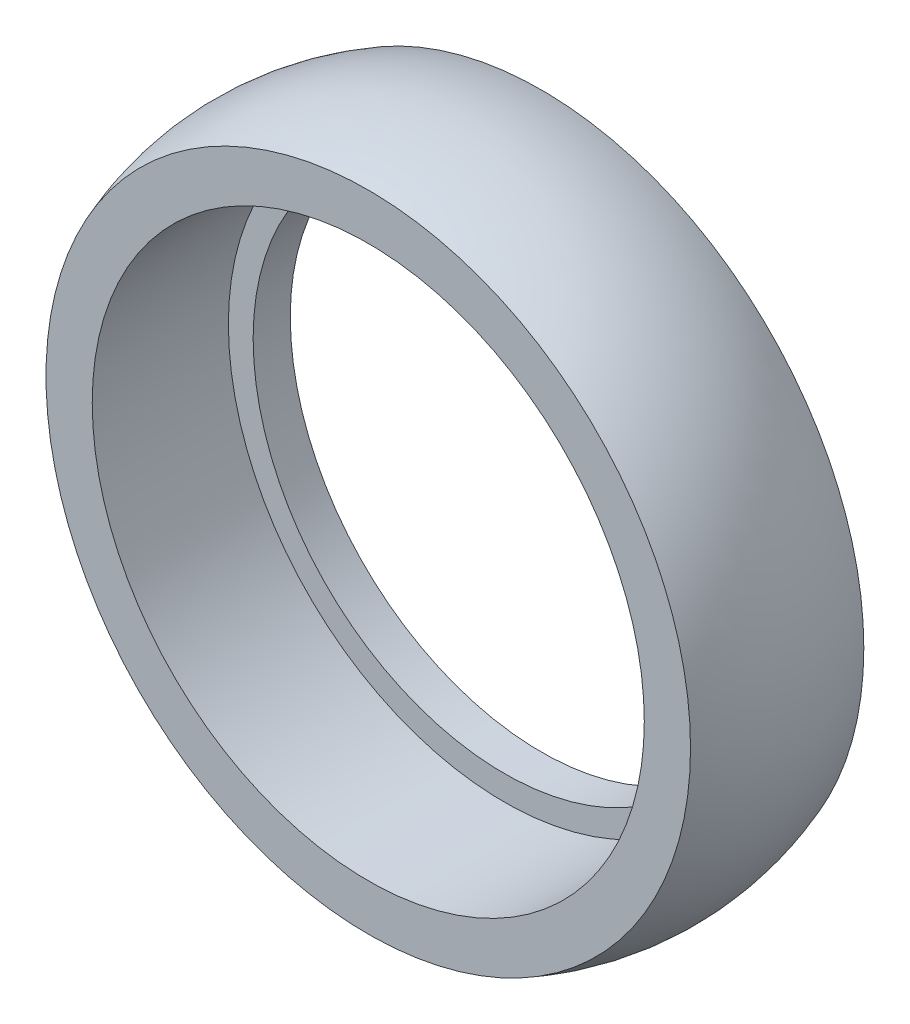
SolidWorks part; units mm, degrees
material "ABS"
ref_plane "Front (1)" through (0, 0, 0) normal (0, 0, 1) x (1, 0, 0)
ref_plane "Top (2)" through (0, 0, 0) normal (0, 1, 0) x (1, 0, 0)
ref_plane "Right (3)" through (0, 0, 0) normal (1, 0, 0) x (0, 0, -1)
ref_axis "X Axis" through (13.5064, 0, 0) along (-1, 0, 0)
ref_axis "Y Axis" through (0, 12.3593, 0) along (0, -1, 0)
ref_axis "Z Axis" through (0, 0, 14.1119) along (0, 0, -1)
sketch "Sketch2" plane through (0, 0, 0) normal (1, 0, 0) x (0, 0, -1)
  line L0 (0, 0) -> (8.188, 0) construction
  line L1 (-3.5, 13.0175) -> (-3.5, 11.15) construction
  line L2 (-7, 13.0175) -> (0, 13.0175) construction
  line L3 (-7, 13.0175) -> (-7, 11.15)
  line L4 (-1.5, 10.15) -> (0, 10.15)
  line L5 (0, 13.0175) -> (0, 10.15)
  line L8 (-7, 11.15) -> (-1.5, 11.15)
  line L9 (-1.5, 10.15) -> (-1.5, 11.15)
  arc A0 (0, 13.0175) -> (-7, 13.0175) centre (-3.5, 3.65) ccw
  dimension "D6" = 10
  dimension "D1" = 22.3
  dimension "D2" = 4
  dimension "D3" = 7
  dimension "D4" = 27.3
  dimension "D5" = 1
  dimension "D7" = 2.5
revolve "Revolve1" add sketch "Sketch2" angle 360 about L0
